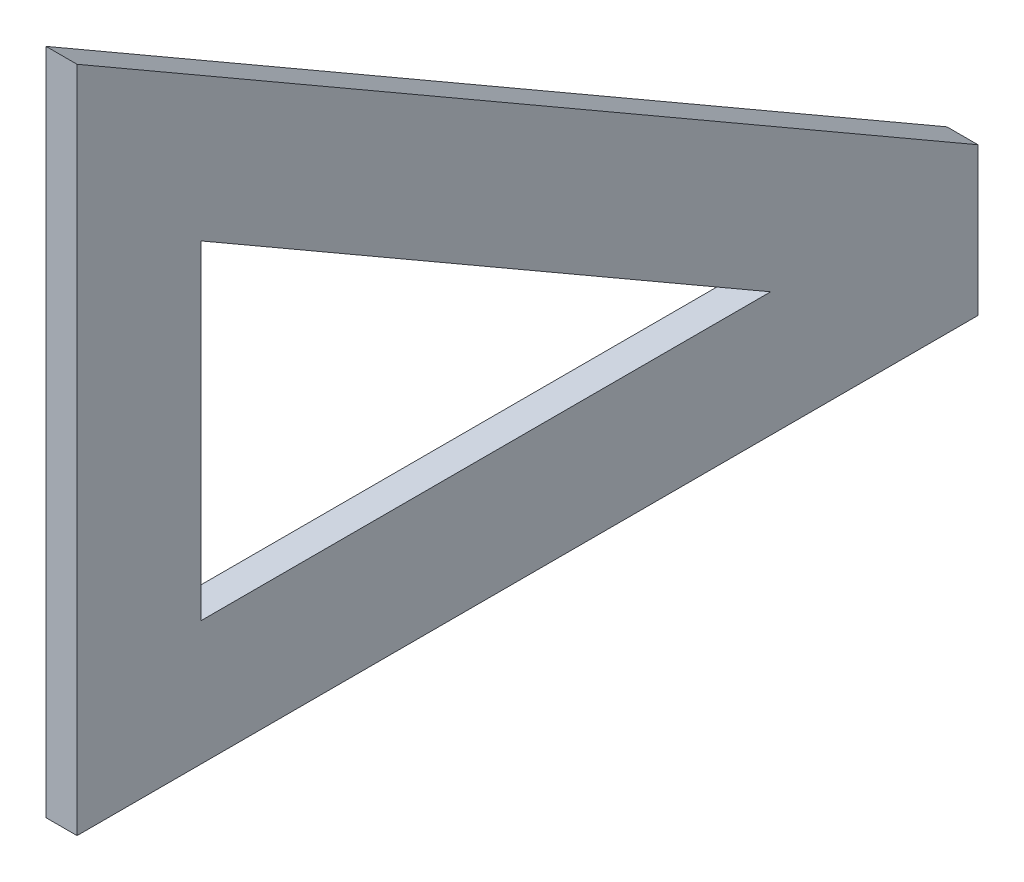
SolidWorks part; units mm, degrees
ref_plane "Front Plane" through (0, 0, 0) normal (0, 0, 1) x (1, 0, 0)
ref_plane "Top Plane" through (0, 0, 0) normal (0, 1, 0) x (1, 0, 0)
ref_plane "Right Plane" through (0, 0, 0) normal (1, 0, 0) x (0, 0, -1)
sketch "Sketch1" plane through (-32.0384, 0, 0) normal (-1, 0, 0) x (0, 0, 1)
  line L0 (-213.5096, 95.25) -> (-213.5096, 125.4926)
  line L1 (165.3114, 95.25) -> (-215.9, 95.25) construction
  line L2 (-213.5096, 125.4926) -> (-29.2385, 231.8816)
  line L3 (-29.2385, 231.8816) -> (-29.2385, 95.25)
  line L4 (-29.2385, 95.25) -> (-213.5096, 95.25)
  line L5 (-29.2385, 231.8816) -> (-130.8385, 173.2228) construction
  line L6 (-29.2385, 95.25) -> (-29.2385, 231.8816) construction
extrude "Boss-Extrude1" add sketch "Sketch1" along normal mid plane 6.35
sketch "Sketch2" plane through (-35.2134, 0, 0) normal (-1, 0, 0) x (0, 0, 1)
  line L14 (-54.6385, 120.65) -> (-54.6385, 187.8875)
  line L15 (-171.0972, 120.65) -> (-54.6385, 120.65)
  line L16 (-54.6385, 187.8875) -> (-171.0972, 120.65)
  line L17 (-54.6385, 120.65) -> (-54.6385, 187.8875)
  line L18 (-171.0972, 120.65) -> (-54.6385, 120.65)
  line L19 (-54.6385, 187.8875) -> (-171.0972, 120.65)
  dimension "D1" = 25.4
extrude "Cut-Extrude1" cut sketch "Sketch2" against normal blind 6.35
